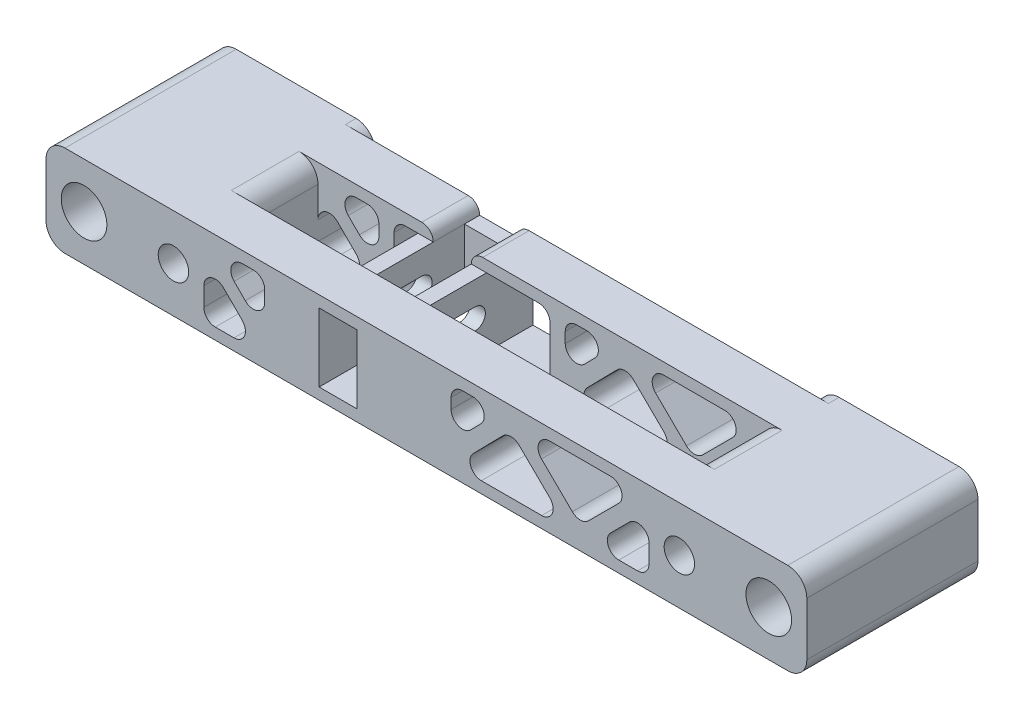
SolidWorks part; units mm, degrees
ref_plane "Front Plane" through (0, 0, 0) normal (0, 0, 1) x (1, 0, 0)
ref_plane "Top Plane" through (0, 0, 0) normal (0, 1, 0) x (1, 0, 0)
ref_plane "Right Plane" through (0, 0, 0) normal (1, 0, 0) x (0, 0, -1)
sketch "Sketch1" plane through (0, 0, 0) normal (0, 0, 1) x (1, 0, 0)
  line L0 (-58.5, 24) -> (-58.5, 0) construction
  line L1 (0, 0) -> (-100, 0)
  line L2 (0, 0) -> (0, 24)
  line L3 (0, 24) -> (-100, 24)
  line L4 (-100, 0) -> (-100, 24)
  circle A0 centre (-90, 12) radius 6
  circle A1 centre (-66.5, 12) radius 4
  point P9 (-100, 12)
  dimension "D3" = 12
  dimension "D4" = 8
  dimension "D1" = 100
  dimension "D2" = 24
  dimension "D5" = 23.5
  dimension "D6" = 10
  dimension "D7" = 8
  dimension "D8" = 41.5
extrude "Boss-Extrude1" add sketch "Sketch1" along normal blind 40
sketch "Sketch2" plane through (0, 0, 0) normal (0, 0, -1) x (-1, 0, 0)
  line L1 (100, 24) -> (0, 24)
  line L2 (100, 24) -> (100, 0)
  line L3 (100, 0) -> (0, 0)
  line L4 (0, 24) -> (0, 0)
extrude "Boss-Extrude2" add sketch "Sketch2" along normal blind 5
sketch "Sketch3" plane through (0, 24, 0) normal (0, 1, 0) x (1, 0, 0)
  line L0 (0, -40) -> (0, 5) construction
  line L1 (0, 5) -> (-58.5, 5)
  line L2 (0, 5) -> (0, -27.8)
  line L3 (0, -27.8) -> (-58.5, -27.8)
  line L4 (-58.5, 5) -> (-58.5, -27.8)
  line L5 (-100, -40) -> (-100, 5) construction
  line L7 (0, -40) -> (-100, -40) construction
  line L8 (-100, 5) -> (0, 5) construction
  dimension "D1" = 41.5
  dimension "D3" = 12.2
extrude "Cut-Extrude1" cut sketch "Sketch3" against normal up to next
mirror "Mirror2" of "Boss-Extrude2", "Cut-Extrude1", "Boss-Extrude1"
sketch "Sketch4" plane through (0, 0, 27.8) normal (0, 0, -1) x (-1, 0, 0)
  line L0 (58.5, 0) -> (58.5, 24) construction
  line L1 (28.2, 3) -> (18.2, 3)
  line L2 (28.2, 3) -> (28.2, 21)
  line L3 (28.2, 21) -> (18.2, 21)
  line L4 (18.2, 3) -> (18.2, 21)
  line L5 (28.2, 3) -> (18.2, 21) construction
  line L6 (28.2, 21) -> (18.2, 3) construction
  point P0 (23.2, 12)
  point P7 (58.5, 12)
  dimension "D1" = 30.3
  dimension "D2" = 10
  dimension "D3" = 18
extrude "Cut-Extrude2" cut sketch "Sketch4" against normal through all
sketch "Sketch5" plane through (0, 0, 27.8) normal (0, 0, -1) x (-1, 0, 0)
  line L0 (18.2, 3) -> (28.2, 3) construction
  line L1 (28.2, 21) -> (32.2, 21)
  line L2 (28.2, 21) -> (28.2, 3)
  line L3 (28.2, 3) -> (32.2, 3)
  line L4 (32.2, 21) -> (32.2, 3)
  line L5 (18.2, 21) -> (14.2, 21)
  line L6 (18.2, 21) -> (18.2, 3)
  line L7 (18.2, 3) -> (14.2, 3)
  line L8 (14.2, 21) -> (14.2, 3)
  dimension "D1" = 4
  dimension "D2" = 4
extrude "Boss-Extrude3" add sketch "Sketch5" along normal blind 26
sketch "Sketch6" plane through (0, 0, 1.8) normal (0, 0, -1) x (-1, 0, 0)
  line L1 (14.2, 21) -> (32.2, 21)
  line L2 (14.2, 21) -> (14.2, 3)
  line L3 (14.2, 3) -> (32.2, 3)
  line L4 (32.2, 21) -> (32.2, 3)
extrude "Boss-Extrude4" add sketch "Sketch6" along normal blind 4
sketch "Sketch7" plane through (-14.2, 0, 0) normal (1, 0, 0) x (0, 0, -1)
  line L0 (-22.05, 12) -> (-13.05, 12) construction
  line L1 (-22.05, 14.75) -> (-13.05, 14.75)
  line L2 (-22.05, 9.25) -> (-13.05, 9.25)
  line L3 (-27.8, 21) -> (-27.8, 3) construction
  line L4 (2.2, 21) -> (-27.8, 21) construction
  arc A0 (-22.05, 14.75) -> (-22.05, 9.25) centre (-22.05, 12) ccw
  arc A1 (-13.05, 9.25) -> (-13.05, 14.75) centre (-13.05, 12) ccw
  point P2 (-17.55, 12)
  point P7 (-24.8, 12)
  dimension "D1" = 9
  dimension "D2" = 5.5
  dimension "D3" = 3
  dimension "D4" = 9
extrude "Cut-Extrude3" cut sketch "Sketch7" against normal up to vertex
sketch "Sketch8" plane through (0, 21, 0) normal (0, 1, 0) x (1, 0, 0)
  line L0 (-32.2, 2.2) -> (-14.2, 2.2) construction
  line L1 (-18.2, 2.2) -> (58.5, 2.2)
  line L2 (-18.2, 2.2) -> (-18.2, -10)
  line L3 (-18.2, -10) -> (58.5, -10)
  line L4 (58.5, 2.2) -> (58.5, -10)
  line L5 (-58.5, 5) -> (-58.5, -27.8) construction
  line L6 (-28.2, 2.2) -> (-58.5, 2.2)
  line L7 (-28.2, 2.2) -> (-28.2, -10)
  line L8 (-28.2, -10) -> (-58.5, -10)
  line L9 (-58.5, 2.2) -> (-58.5, -10)
  line L10 (-28.2, -1.8) -> (-28.2, -27.8) construction
  line L11 (-18.2, -1.8) -> (-18.2, -27.8) construction
  line L12 (58.5, 5) -> (58.5, -27.8) construction
  dimension "D1" = 12.2
  dimension "D2" = 12.2
extrude "Boss-Extrude5" add sketch "Sketch8" along normal up to vertex (3 mm away) up to point (-58.5, 24, -5)
ref_plane "Plane1" through (0, 12, 0) normal (0, 1, 0) x (1, 0, 0)
mirror "Mirror4" about plane through (0, 12, 0) normal (0, 1, 0) of "Boss-Extrude5"
sketch "Sketch9" plane through (0, 0, -2.2) normal (0, 0, -1) x (-1, 0, 0)
  line L0 (-58.5, 21) -> (-40.5, 3) construction
  line L1 (-58.5, 3) -> (14.2, 3) construction
  line L2 (-40.5, 3) -> (-22.15, 21) construction
  line L3 (-58.5, 21) -> (14.2, 21) construction
  line L4 (-22.15, 21) -> (-4.4933, 3) construction
  line L5 (-4.4933, 3) -> (-4.4933, 21) construction
  line L6 (58.5, 21) -> (40.5, 3) construction
  line L7 (32.2, 3) -> (58.5, 3) construction
  line L8 (40.5, 3) -> (40.5, 21) construction
  line L9 (32.2, 21) -> (58.5, 21) construction
  line L10 (-58.5, 0) -> (-58.5, 24) construction
  line L11 (58.5, 0) -> (58.5, 24) construction
  line L12 (-58.5, 18.1716) -> (-43.3284, 3)
  line L13 (-37.6439, 3) -> (-22.1772, 18.1717)
  line L14 (-22.1772, 18.1717) -> (-7.2949, 3)
  line L15 (-2.4933, 3) -> (-2.4933, 21)
  line L16 (55.6716, 21) -> (42.5, 7.8284)
  line L17 (42.5, 7.8284) -> (42.5, 21)
  line L18 (-55.6716, 21) -> (-40.4864, 5.8149)
  line L19 (-40.4864, 5.8149) -> (-25.0061, 21)
  line L20 (-19.3484, 21) -> (-6.4933, 7.8949)
  line L21 (-6.4933, 7.8949) -> (-6.4933, 21)
  line L22 (58.5, 18.1716) -> (43.3284, 3)
  line L23 (38.5, 3) -> (38.5, 21)
  line L24 (-58.5, 18.1716) -> (-58.5, 21)
  line L25 (-58.5, 21) -> (-55.6716, 21)
  line L26 (-6.4933, 21) -> (-2.4933, 21)
  line L27 (-7.2949, 3) -> (-2.4933, 3)
  line L28 (-37.6439, 3) -> (-43.3284, 3)
  line L29 (-25.0061, 21) -> (-19.3484, 21)
  line L30 (-57.0858, 22.4142) -> (-40.4864, 5.8149) construction
  line L31 (-59.9142, 19.5858) -> (-40.5136, 0.1851) construction
  line L32 (-40.5136, 0.1851) -> (-22.1772, 18.1717) construction
  line L33 (-22.1772, 18.1717) -> (-2.4933, -1.8949) construction
  line L34 (-2.4933, -1.8949) -> (-2.4933, 21) construction
  line L35 (-22.1228, 23.8283) -> (-6.4933, 7.8949) construction
  line L36 (-40.4864, 5.8149) -> (-22.1228, 23.8283) construction
  line L37 (38.5, 21) -> (42.5, 21)
  line L38 (55.6716, 21) -> (58.5, 21)
  line L39 (58.5, 21) -> (58.5, 18.1716)
  line L40 (58.5, 0) -> (58.5, 24) construction
  line L41 (43.3284, 3) -> (38.5, 3)
  line L42 (38.5, -1.8284) -> (38.5, 21) construction
  line L43 (59.9142, 19.5858) -> (38.5, -1.8284) construction
  line L44 (57.0858, 22.4142) -> (42.5, 7.8284) construction
  dimension "D1" = 45
  dimension "D2" = 45
  dimension "D3" = 2
  dimension "D4" = 2
extrude "Boss-Extrude6" add sketch "Sketch9" against normal up to vertex (12.2 mm away) up to point (-14.2, 21, 10)
fillet "Fillet1" radius 5 14 edges at (58.5, 24, 18.9) (-58.5, 24, 18.9) (58.5, 0, -3.6) (58.5, 3, 3.9) (-58.5, 0, -3.6) (-58.5, 3, 3.9) (-58.5, 24, -3.6) (-58.5, 0, 18.9) (100, 0, 17.5) (100, 24, 17.5) (-100, 0, 17.5) (-100, 24, 17.5) (58.5, 0, 18.9) (58.5, 24, -3.6)
fillet "Fillet2" radius 3 38 edges at (-30.2, 3, 27.8) (-30.2, 21, 27.8) (-16.2, 21, 27.8) (-16.2, 3, 27.8) (-18.2, 22.5, -2.2) (-18.2, 22.5, 10) (-18.2, 24, 3.9) (-28.2, 22.5, 10) (-28.2, 22.5, -2.2) (-28.2, 24, 3.9) (-18.2, 0, 3.9) (-18.2, 1.5, 10) (-18.2, 1.5, -2.2) (-28.2, 0, 3.9) (-28.2, 1.5, -2.2) (-28.2, 1.5, 10) (55.6716, 21, 3.9) (40.4864, 5.8149, 3.9) (25.0061, 21, 3.9) (19.3484, 21, 3.9) (6.4933, 7.8949, 3.9) (6.4933, 21, 3.9) (2.4933, 21, 3.9) (2.4933, 3, 3.9) (7.2949, 3, 3.9) (22.1772, 18.1717, 3.9) (37.6439, 3, 3.9) (43.3284, 3, 3.9) (58.5, 18.1716, 3.9) (-58.5, 18.1716, 3.9) (-43.3284, 3, 3.9) (-38.5, 3, 3.9) (-38.5, 21, 3.9) (-42.5, 21, 3.9) (-42.5, 7.8284, 3.9) (-55.6716, 21, 3.9) (58.9174, 3, 3.9) (-58.9174, 3, 3.9)
sketch "Sketch10" plane through (0, 0, 40) normal (0, 0, 1) x (1, 0, 0)
  line L0 (42.5874, 7.9159) -> (50.5503, 15.8787) construction
  line L1 (30.2477, 15.8584) -> (38.3653, 7.8955) construction
  line L2 (32.3485, 21) -> (48.4289, 21) construction
  line L3 (53.3787, 13.0503) -> (48.4497, 8.1213) construction
  line L4 (50.5711, 3) -> (55.5, 3) construction
  line L5 (32.4023, 8.1416) -> (24.3189, 16.0709) construction
  line L6 (20.0764, 16.0301) -> (12.2984, 8.1008) construction
  line L7 (14.4401, 3) -> (30.3015, 3) construction
  line L8 (11.635, 13.1366) -> (14.3449, 15.8992) construction
  line L9 (9.4933, 21) -> (12.2033, 21) construction
  line L10 (6.4933, 18) -> (6.4933, 15.2374) construction
  line L11 (-48.4289, 21) -> (-45.5, 21) construction
  line L12 (-42.5, 15.0711) -> (-42.5, 18) construction
  line L13 (-50.5503, 15.8787) -> (-47.6213, 12.9497) construction
  line L14 (-55.5, 3) -> (-50.5711, 3) construction
  line L15 (-55.5, 3) -> (-50.5711, 3)
  line L16 (-50.5503, 15.8787) -> (-47.6213, 12.9497)
  line L17 (-42.5, 15.0711) -> (-42.5, 18)
  line L18 (-48.4289, 21) -> (-45.5, 21)
  line L19 (6.4933, 18) -> (6.4933, 15.2374)
  line L20 (9.4933, 21) -> (12.2033, 21)
  line L21 (11.635, 13.1366) -> (14.3449, 15.8992)
  line L22 (14.4401, 3) -> (30.3015, 3)
  line L23 (20.0764, 16.0301) -> (12.2984, 8.1008)
  line L24 (32.4023, 8.1416) -> (24.3189, 16.0709)
  line L25 (50.5711, 3) -> (55.5, 3)
  line L26 (53.3787, 13.0503) -> (48.4497, 8.1213)
  line L27 (32.3485, 21) -> (48.4289, 21)
  line L28 (30.2477, 15.8584) -> (38.3653, 7.8955)
  line L29 (42.5874, 7.9159) -> (50.5503, 15.8787)
  line L30 (-48.4497, 8.1213) -> (-53.3787, 13.0503) construction
  line L31 (-48.4497, 8.1213) -> (-53.3787, 13.0503)
  line L32 (-58.5, 10.9289) -> (-58.5, 6)
  line L33 (58.5, 10.9289) -> (58.5, 6)
  arc A0 (-50.5711, 3) -> (-48.4497, 8.1213) centre (-50.5711, 6) ccw construction
  arc A1 (38.3653, 7.8955) -> (42.5874, 7.9159) centre (40.4661, 10.0372) ccw construction
  arc A2 (32.3485, 21) -> (30.2477, 15.8584) centre (32.3485, 18) ccw construction
  arc A3 (50.5503, 15.8787) -> (48.4289, 21) centre (48.4289, 18) ccw construction
  arc A4 (58.5, 10.9289) -> (53.3787, 13.0503) centre (55.5, 10.9289) ccw construction
  arc A5 (48.4497, 8.1213) -> (50.5711, 3) centre (50.5711, 6) ccw construction
  arc A6 (55.5, 3) -> (58.5, 6) centre (55.5, 6) ccw construction
  arc A7 (24.3189, 16.0709) -> (20.0764, 16.0301) centre (22.2181, 13.9293) ccw construction
  arc A8 (12.2984, 8.1008) -> (14.4401, 3) centre (14.4401, 6) ccw construction
  arc A9 (30.3015, 3) -> (32.4023, 8.1416) centre (30.3015, 6) ccw construction
  arc A10 (14.3449, 15.8992) -> (12.2033, 21) centre (12.2033, 18) ccw construction
  arc A11 (9.4933, 21) -> (6.4933, 18) centre (9.4933, 18) ccw construction
  arc A12 (6.4933, 15.2374) -> (11.635, 13.1366) centre (9.4933, 15.2374) ccw construction
  arc A13 (-42.5, 18) -> (-45.5, 21) centre (-45.5, 18) ccw construction
  arc A14 (-48.4289, 21) -> (-50.5503, 15.8787) centre (-48.4289, 18) ccw construction
  arc A15 (-47.6213, 12.9497) -> (-42.5, 15.0711) centre (-45.5, 15.0711) ccw construction
  arc A16 (-50.5711, 3) -> (-48.4497, 8.1213) centre (-50.5711, 6) ccw
  arc A17 (-47.6213, 12.9497) -> (-42.5, 15.0711) centre (-45.5, 15.0711) ccw
  arc A18 (-48.4289, 21) -> (-50.5503, 15.8787) centre (-48.4289, 18) ccw
  arc A19 (-42.5, 18) -> (-45.5, 21) centre (-45.5, 18) ccw
  arc A20 (6.4933, 15.2374) -> (11.635, 13.1366) centre (9.4933, 15.2374) ccw
  arc A21 (9.4933, 21) -> (6.4933, 18) centre (9.4933, 18) ccw
  arc A22 (14.3449, 15.8992) -> (12.2033, 21) centre (12.2033, 18) ccw
  arc A23 (30.3015, 3) -> (32.4023, 8.1416) centre (30.3015, 6) ccw
  arc A24 (12.2984, 8.1008) -> (14.4401, 3) centre (14.4401, 6) ccw
  arc A25 (24.3189, 16.0709) -> (20.0764, 16.0301) centre (22.2181, 13.9293) ccw
  arc A26 (55.5, 3) -> (58.5, 6) centre (55.5, 6) ccw
  arc A27 (48.4497, 8.1213) -> (50.5711, 3) centre (50.5711, 6) ccw
  arc A28 (58.5, 10.9289) -> (53.3787, 13.0503) centre (55.5, 10.9289) ccw
  arc A29 (50.5503, 15.8787) -> (48.4289, 21) centre (48.4289, 18) ccw
  arc A30 (32.3485, 21) -> (30.2477, 15.8584) centre (32.3485, 18) ccw
  arc A31 (38.3653, 7.8955) -> (42.5874, 7.9159) centre (40.4661, 10.0372) ccw
  arc A32 (-58.5, 6) -> (-55.5, 3) centre (-55.5, 6) ccw construction
  arc A33 (-53.3787, 13.0503) -> (-58.5, 10.9289) centre (-55.5, 10.9289) ccw construction
  arc A34 (-58.5, 6) -> (-55.5, 3) centre (-55.5, 6) ccw
  arc A35 (-53.3787, 13.0503) -> (-58.5, 10.9289) centre (-55.5, 10.9289) ccw
extrude "Cut-Extrude4" cut sketch "Sketch10" against normal up to vertex (12.2 mm away) up to point (63.5, 24, 27.8)
